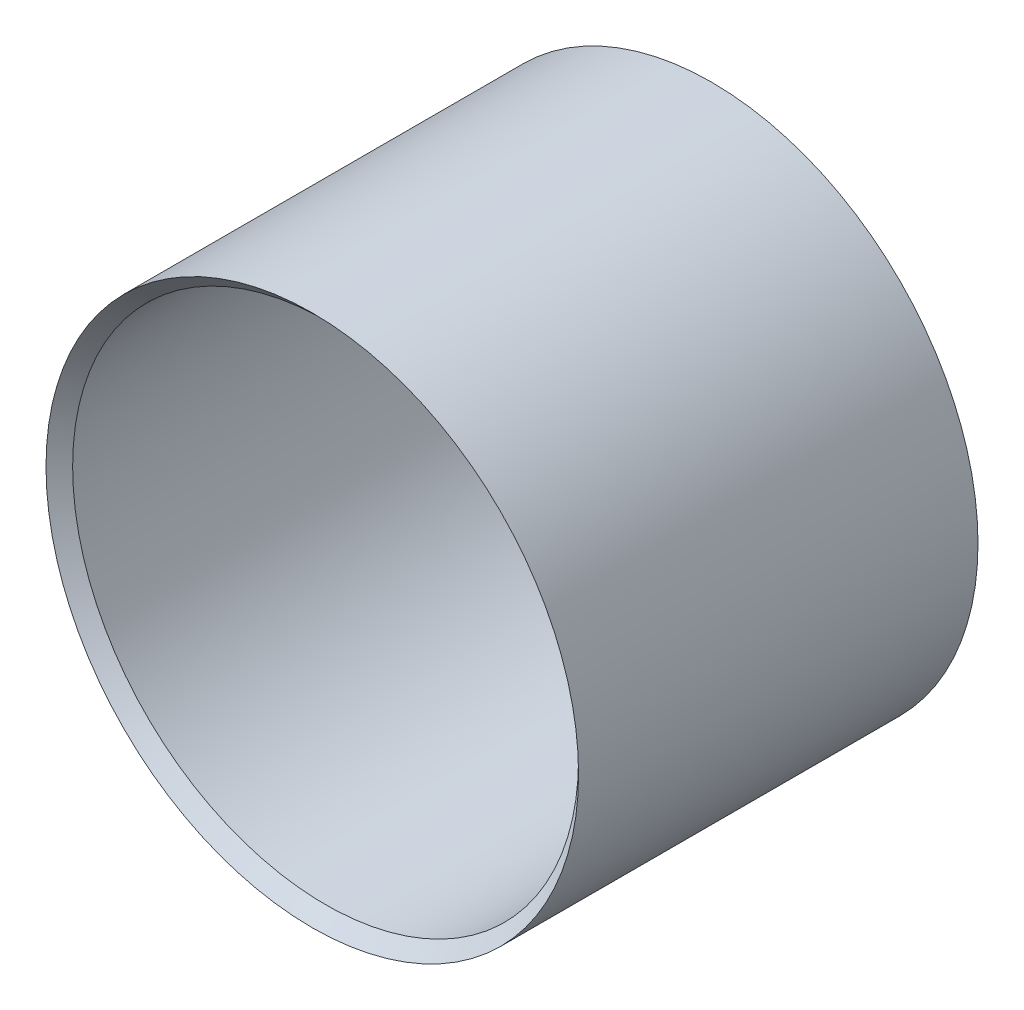
SolidWorks part; units mm, degrees
ref_plane "Front Plane" through (0, 0, 0) normal (0, 0, 1) x (1, 0, 0)
ref_plane "Top Plane" through (0, 0, 0) normal (0, 1, 0) x (1, 0, 0)
ref_plane "Right Plane" through (0, 0, 0) normal (1, 0, 0) x (0, 0, -1)
sketch "Sketch1" plane through (0, 0, 0) normal (0, 0, 1) x (1, 0, 0)
  circle A0 centre (0, 0) radius 10
  circle A1 centre (0, 0) radius 9.5
  dimension "D1" = 20
  dimension "D2" = 19
extrude "Boss-Extrude1" add sketch "Sketch1" along normal blind 16
chamfer "Chamfer1" distance 1 angle 45 2 edges at (9.5, 0, 0) (9.5, 0, 16)
